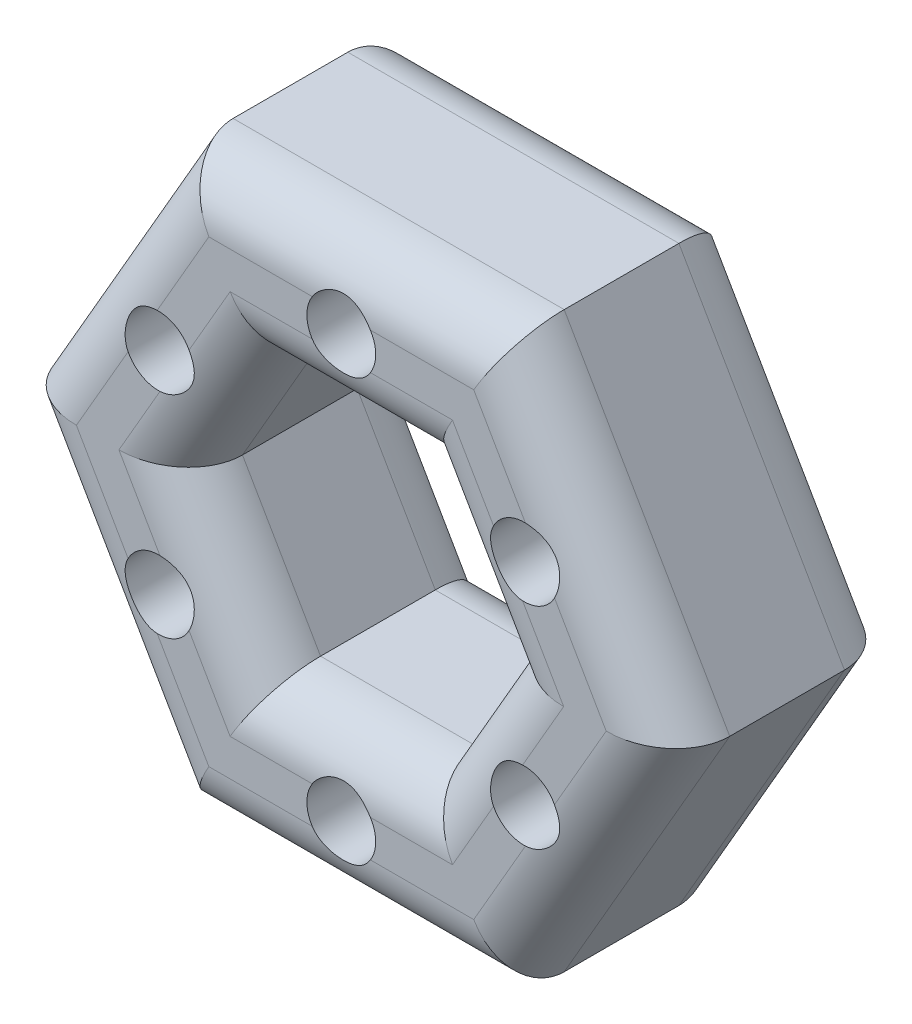
SolidWorks part; units mm, degrees
ref_plane "Płaszczyzna przednia" through (0, 0, 0) normal (0, 0, 1) x (1, 0, 0)
ref_plane "Płaszczyzna górna" through (0, 0, 0) normal (0, 1, 0) x (1, 0, 0)
ref_plane "Płaszczyzna prawa" through (0, 0, 0) normal (1, 0, 0) x (0, 0, -1)
sketch "Szkic1" plane through (0, 0, 0) normal (0, 0, 1) x (1, 0, 0)
  line L6 (-28.8675, 50) -> (28.8675, 50)
  line L7 (28.8675, 50) -> (57.735, 0)
  line L8 (57.735, 0) -> (28.8675, -50)
  line L9 (28.8675, -50) -> (-28.8675, -50)
  line L10 (-28.8675, -50) -> (-57.735, 0)
  line L11 (-57.735, 0) -> (-28.8675, 50)
  line L12 (-13.6139, 23.58) -> (13.6139, 23.58)
  line L13 (13.6139, 23.58) -> (27.2278, 0)
  line L14 (27.2278, 0) -> (13.6139, -23.58)
  line L15 (13.6139, -23.58) -> (-13.6139, -23.58)
  line L16 (-13.6139, -23.58) -> (-27.2278, 0)
  line L17 (-27.2278, 0) -> (-13.6139, 23.58)
  circle A1 centre (0, 36.79) radius 6
  circle A2 centre (31.8611, 18.395) radius 6
  circle A3 centre (31.8611, -18.395) radius 6
  circle A4 centre (0, -36.79) radius 6
  circle A5 centre (-31.8611, -18.395) radius 6
  circle A6 centre (-31.8611, 18.395) radius 6
  point P18 (0, 0)
  point P25 (0, 0)
  dimension "D2" = 12
  dimension "D6" = 26.42
  dimension "D3" = 6
extrude "Dodanie-wyciągnięcie1" add sketch "Szkic1" along normal mid plane 40
fillet "Zaokrąglenie1" radius 10 24 edges at (-20.4209, 11.79, -20) (-20.4209, -11.79, -20) (0, -23.58, -20) (20.4209, -11.79, -20) (20.4209, 11.79, -20) (0, 23.58, -20) (-43.3013, -25, -20) (0, -50, -20) (43.3013, -25, -20) (43.3013, 25, -20) (0, 50, -20) (-43.3013, 25, -20) (0, -23.58, 20) (20.4209, -11.79, 20) (20.4209, 11.79, 20) (0, 23.58, 20) (-20.4209, 11.79, 20) (-20.4209, -11.79, 20) (-43.3013, -25, 20) (0, -50, 20) (43.3013, -25, 20) (43.3013, 25, 20) (-43.3013, 25, 20) (0, 50, 20)
